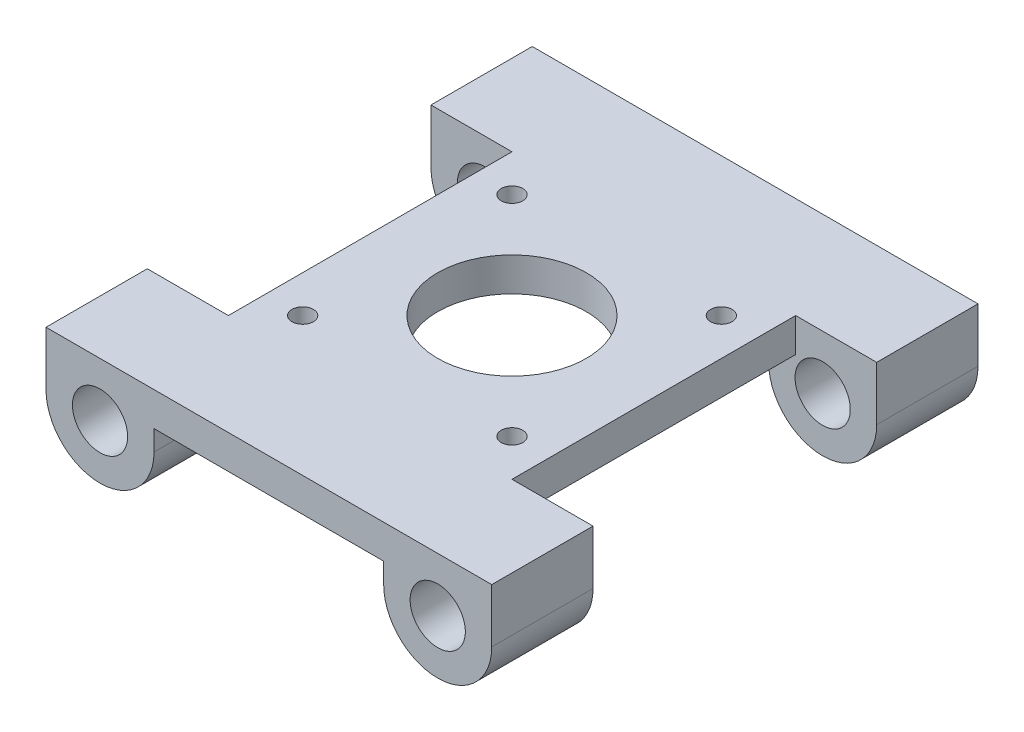
SolidWorks part; units mm, degrees
material "ABS"
ref_plane "Front Plane" through (0, 0, 0) normal (0, 0, 1) x (1, 0, 0)
ref_plane "Top Plane" through (0, 0, 0) normal (0, 1, 0) x (1, 0, 0)
ref_plane "Right Plane" through (0, 0, 0) normal (1, 0, 0) x (0, 0, -1)
sketch "Sketch1" plane through (0, 0, 0) normal (0, 0, 1) x (1, 0, 0)
  line L0 (0, 74.8863) -> (0, -94.3789) construction
  line L1 (33, 0) -> (-33, 0)
  line L2 (-33, 0) -> (-33, -8)
  line L3 (17, -5) -> (-17, -5)
  line L4 (-17, -5) -> (-17, -8)
  line L5 (17, -5) -> (17, -8)
  line L6 (33, 0) -> (33, -8)
  circle A0 centre (-25, -8) radius 4.0875
  arc A1 (-33, -8) -> (-17, -8) centre (-25, -8) ccw
  arc A2 (33, -8) -> (17, -8) centre (25, -8) cw
  circle A3 centre (25, -8) radius 4.0875
  point P16 (0, -5)
  point P17 (0, 0)
  dimension "D1" = 8.175
  dimension "D5" = 8
  dimension "D2" = 25
  dimension "D3" = 8
  dimension "D4" = 5
extrude "Boss-Extrude1" add sketch "Sketch1" against normal blind 15
sketch "Sketch2" plane through (0, 0, -15) normal (0, 0, -1) x (-1, 0, 0)
  line L0 (21, 0) -> (-21, 0)
  line L1 (-33, 0) -> (33, 0) construction
  line L2 (-21, 0) -> (-21, -5)
  line L3 (-21, -5) -> (21, -5)
  line L4 (17, -5) -> (-17, -5) construction
  line L5 (0, 7.9638) -> (0, -15.9981) construction
  line L6 (21, 0) -> (21, -5)
  point P12 (0, -5)
  point P13 (0, 0)
  dimension "D1" = 21
extrude "Boss-Extrude2" add sketch "Sketch2" along normal blind 42
extrude "Boss-Extrude3" add sketch "Sketch1<2>" against normal blind 15 from vertex starting at point (-21, 0, -57)
sketch "Sketch1<2>" plane through (0, 0, 0) normal (0, 0, 1) x (1, 0, 0) same geometry as "Sketch1"
sketch "Sketch3" plane through (0, 0, 0) normal (0, 1, 0) x (1, 0, 0)
  line L0 (0, -9.6218) -> (0, 80.5515) construction
  line L1 (-21, 36) -> (21, 36) construction
  line L2 (-21, 57) -> (-21, 15) construction
  line L3 (21, 57) -> (21, 15) construction
  circle A0 centre (-15.5, 51.5) radius 1.5875
  circle A1 centre (0, 36) radius 11
  circle A2 centre (15.5, 51.5) radius 1.5875
  circle A3 centre (15.5, 20.5) radius 1.5875
  circle A4 centre (-15.5, 20.5) radius 1.5875
  dimension "D1" = 3.175
  dimension "D4" = 22
  dimension "D2" = 15.5
  dimension "D3" = 15.5
  dimension "D5" = 2
  dimension "D6" = 2
extrude "Cut-Extrude1" cut sketch "Sketch3" against normal through all
ref_axis "X Axis" through (36.3, 0, 0) along (-1, 0, 0)
ref_axis "Y Axis" through (0, 0, -75.6) along (0, 0, 1)
equation "\"rod_diameter\"= 8"
equation "\"rod_hole_thickness\"= 4"
equation "\"rod_radius\"= \"rod_diameter\" / 2"
equation "\"platter_diameter\"= 320"
equation "\"platter_radius\"= \"platter_diameter\" / 2"
equation "\"extruder_mount_hole_spacing\"= 75"
equation "\"arm_rod_spacing\"= 40"
equation "\"motor_level_rod_spacing\"= 15"
equation "\"linear_bearing_diameter\"= 15"
equation "\"z_rod_spacing\"= 75"
equation "\"platter_rod_spacing\"= 50"
equation "\"rod_nut_thickness\"= 6.5"
equation "\"rod_nut_inscribed_diameter\"= 13"
equation "\"z_height\"= 400"
equation "\"D1@Sketch1\"=\"rod_diameter\"+\"printed_hole_tolerance\""
equation "\"D2@Sketch1\"=\"platter_rod_spacing\"/2"
equation "\"D3@Sketch1\"=\"rod_radius\"+\"rod_hole_thickness\""
equation "\"D5@Sketch1\"=\"rod_radius\"+\"rod_hole_thickness\""
equation "\"D2@Sketch3\"=31/2"
equation "\"top_frame_spacing\"= 100"
equation "\"z_drive_rod_offset\"= 12"
equation "\"gear_pitch\"=2"
equation "\"r_gear_teeth\"= 450"
equation "\"theta_gear_teeth\"= 385"
equation "\"sheet_thickness\"=5.333"
equation "\"sheet_tab_hole_thickness\"= \"sheet_thickness\""
equation "\"sheet_tab_width\"= \"sheet_thickness\"*2"
equation "\"sheet_double_tab_width\"= 35"
equation "\"sheet_bolt_diameter\"= 3"
equation "\"sheet_bolt_length\"= 16"
equation "\"sheet_nut_diameter\"= 5.5"
equation "\"sheet_nut_thickness\"= 2.5"
equation "\"sheet_nut_depth\"= 10"
equation "\"bearing_outside_diameter\"= 22"
equation "\"bearing_thickness\"= 7"
equation "\"corner_part_thickness\"= \"sheet_thickness\" + \"bearing_thickness\""
equation "\"setscrew_nut_diameter\"= 6"
equation "\"setscrew_nut_thickness\"= 3"
equation "\"setscrew_bolt_diameter\"= 3"
equation "\"motor_shaft_diameter\"= 5.7"
equation "\"printed_hole_tolerance\"= 0.175"
equation "\"D1@Sketch3\"=\"sheet_bolt_diameter\"+\"printed_hole_tolerance\""
